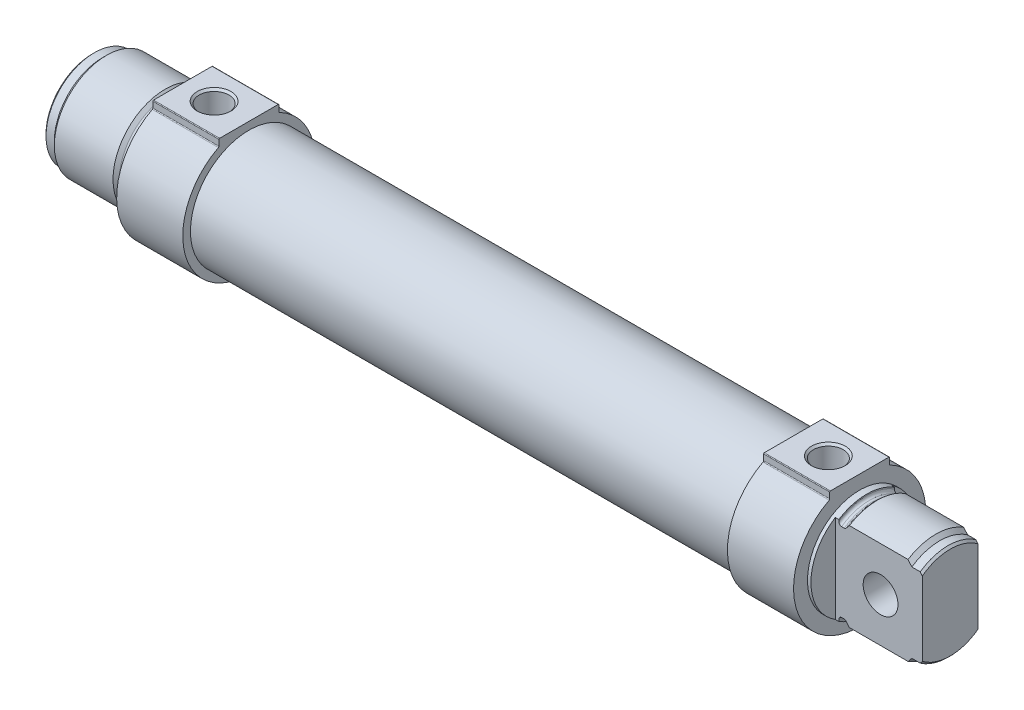
SolidWorks part; units mm, degrees
ref_plane "Ebene vorne" through (0, 0, 0) normal (0, 0, 1) x (1, 0, 0)
ref_plane "Ebene oben" through (0, 0, 0) normal (0, 1, 0) x (1, 0, 0)
ref_plane "Ebene rechts" through (0, 0, 0) normal (1, 0, 0) x (0, 0, -1)
sketch "Skizze1" plane through (0, 0, 0) normal (0, 0, 1) x (1, 0, 0)
  line L0 (0, 0) -> (0, 13.3)
  line L1 (0, 13.3) -> (0.6, 13.9)
  line L2 (0.6, 13.9) -> (3, 13.9)
  line L3 (3, 13.9) -> (4.1, 15)
  line L4 (4.1, 15) -> (20.95, 15)
  line L5 (20.95, 15) -> (21.8657, 14.0843)
  line L6 (22.4314, 13.85) -> (23.2, 13.85)
  line L7 (24, 14.65) -> (24, 15)
  line L8 (24, 15) -> (26, 15)
  line L9 (26, 15) -> (26, 0)
  line L10 (26, 0) -> (0, 0)
  line L11 (26, 0) -> (0, 0) construction
  arc A0 (21.8657, 14.0843) -> (22.4314, 13.85) centre (22.4314, 14.65) ccw
  arc A1 (23.2, 13.85) -> (24, 14.65) centre (23.2, 14.65) ccw
revolve "Rotation1" add sketch "Skizze1" angle 360 about L11 reverse direction yes
cosmetic thread "Gewindedarstellung1" parameters "D1"=17.77, "D2"=28.16
ref_plane "Ebene1" through (32, 0, 0) normal (1, 0, 0) x (0, 0, -1)
ref_plane "Ebene2" through (16, 0, 0) normal (1, 0, 0) x (0, 0, -1)
ref_plane "Ebene3" through (0, -20, 0) normal (0, 1, 0) x (1, 0, 0)
ref_plane "Ebene4" through (0, 15, 0) normal (0, 1, 0) x (1, 0, 0)
ref_plane "Ebene5" through (0, -9.5, 0) normal (0, 1, 0) x (1, 0, 0)
ref_plane "Ebene6" through (0, 9.5, 0) normal (0, 1, 0) x (1, 0, 0)
ref_plane "Ebene7" through (26, 0, 0) normal (1, 0, 0) x (0, 0, -1)
ref_plane "Ebene8" through (26, 0, 0) normal (1, 0, 0) x (0, 0, -1)
ref_plane "Ebene9" through (38.5, 0, 0) normal (1, 0, 0) x (0, 0, -1)
ref_plane "Ebene10" through (31, 0, 0) normal (1, 0, 0) x (0, 0, -1)
ref_plane "Ebene11" through (46, 0, 0) normal (1, 0, 0) x (0, 0, -1)
sketch "Skizze2" plane through (26, 0, 0) normal (1, 0, 0) x (0, 0, -1)
  line L0 (8.6, 17.1254) -> (8.6, 18.8)
  line L1 (8.4, 19) -> (-8.4, 19)
  line L2 (-8.6, 18.8) -> (-8.6, 17.1254)
  arc A0 (-8.7617, 16.8592) -> (8.7617, 16.8592) centre (0, 0) ccw
  arc A1 (8.7617, 16.8592) -> (8.6, 17.1254) centre (8.9, 17.1254) cw
  arc A2 (8.6, 18.8) -> (8.4, 19) centre (8.4, 18.8) ccw
  arc A3 (-8.4, 19) -> (-8.6, 18.8) centre (-8.4, 18.8) ccw
  arc A4 (-8.6, 17.1254) -> (-8.7617, 16.8592) centre (-8.9, 17.1254) cw
extrude "Aufsatz-Linear austragen1" add sketch "Skizze2" along normal blind 19
ref_plane "Ebene12" through (40.5, 0, 0) normal (1, 0, 0) x (0, 0, -1)
ref_plane "Ebene13" through (0, 0, 0) normal (0, 0, 1) x (1, 0, 0)
ref_plane "Ebene14" through (0, 0, -12.8) normal (0, 0, 1) x (1, 0, 0)
ref_plane "Ebene15" through (0, 0, 0) normal (0, 1, 0) x (1, 0, 0)
ref_plane "Ebene16" through (0, 9, 0) normal (0, 1, 0) x (1, 0, 0)
ref_plane "Ebene17" through (0, 0, -6.6) normal (0, 0, 1) x (1, 0, 0)
ref_plane "Ebene18" through (0, 0, 0) normal (0, 1, 0) x (1, 0, 0)
ref_plane "Ebene19" through (0, 9, 0) normal (0, 1, 0) x (1, 0, 0)
ref_plane "Ebene20" through (0, 9.8573, -1.7381) normal (0, 0.9848, -0.1736) x (1, 0, 0)
ref_plane "Ebene21" through (0, 8.3801, -1.4776) normal (0, 0.9848, -0.1736) x (1, 0, 0)
sketch "Skizze3" plane through (0, 0, 0) normal (0, 0, 1) x (1, 0, 0)
  line L0 (45, 0) -> (45, 16.8)
  line L1 (45, 16.8) -> (201.5, 16.8)
  line L2 (201.5, 16.8) -> (201.5, 0)
  line L3 (201.5, 0) -> (45, 0)
  line L4 (201.5, 0) -> (45, 0) construction
revolve "Rotation2" add sketch "Skizze3" angle 360 about L4 reverse direction yes
ref_plane "Ebene22" through (201.5, 0, 0) normal (1, 0, 0) x (0, 0, -1)
sketch "Skizze4" plane through (201.5, 0, 0) normal (1, 0, 0) x (0, 0, -1)
  line L0 (8.6, 17.1254) -> (8.6, 18.8)
  line L1 (8.4, 19) -> (-8.4, 19)
  line L2 (-8.6, 18.8) -> (-8.6, 17.1254)
  arc A0 (-8.7617, 16.8592) -> (8.7617, 16.8592) centre (0, 0) ccw
  arc A1 (8.7617, 16.8592) -> (8.6, 17.1254) centre (8.9, 17.1254) cw
  arc A2 (8.6, 18.8) -> (8.4, 19) centre (8.4, 18.8) ccw
  arc A3 (-8.4, 19) -> (-8.6, 18.8) centre (-8.4, 18.8) ccw
  arc A4 (-8.6, 17.1254) -> (-8.7617, 16.8592) centre (-8.9, 17.1254) cw
extrude "Aufsatz-Linear austragen2" add sketch "Skizze4" along normal blind 19
ref_plane "Ebene23" through (206, 0, 0) normal (1, 0, 0) x (0, 0, -1)
ref_plane "Ebene24" through (206, 0, 0) normal (1, 0, 0) x (0, 0, -1)
ref_plane "Ebene25" through (0, 0, 6.6) normal (0, 0, 1) x (1, 0, 0)
ref_plane "Ebene26" through (0, 0, 0) normal (0, 1, 0) x (1, 0, 0)
ref_plane "Ebene27" through (0, 9, 0) normal (0, 1, 0) x (1, 0, 0)
ref_plane "Ebene28" through (0, 9.8573, 1.7381) normal (0, 0.9848, 0.1736) x (1, 0, 0)
ref_plane "Ebene29" through (0, 8.3801, 1.4776) normal (0, 0.9848, 0.1736) x (1, 0, 0)
ref_plane "Ebene30" through (275.5, 0, 0) normal (1, 0, 0) x (0, 0, -1)
ref_plane "Ebene31" through (263, 0, 0) normal (1, 0, 0) x (0, 0, -1)
ref_plane "Ebene32" through (270.5, 0, 0) normal (1, 0, 0) x (0, 0, -1)
ref_plane "Ebene33" through (255.5, 0, 0) normal (1, 0, 0) x (0, 0, -1)
sketch "Skizze5" plane through (0, 0, 0) normal (0, 0, 1) x (1, 0, 0)
  line L0 (220.5, 0) -> (220.5, 15)
  line L1 (220.5, 15) -> (222.5, 15)
  line L2 (222.5, 15) -> (222.5, 14.65)
  line L3 (223.3, 13.85) -> (224.0686, 13.85)
  line L4 (224.6343, 14.0843) -> (225.55, 15)
  line L5 (225.55, 15) -> (242.4, 15)
  line L6 (242.4, 15) -> (243.5, 13.9)
  line L7 (243.5, 13.9) -> (245.9, 13.9)
  line L8 (245.9, 13.9) -> (246.5, 13.3)
  line L9 (246.5, 13.3) -> (246.5, 0)
  line L10 (246.5, 0) -> (220.5, 0)
  line L11 (246.5, 0) -> (220.5, 0) construction
  arc A0 (222.5, 14.65) -> (223.3, 13.85) centre (223.3, 14.65) ccw
  arc A1 (224.0686, 13.85) -> (224.6343, 14.0843) centre (224.0686, 14.65) ccw
revolve "Rotation3" add sketch "Skizze5" angle 360 about L11 reverse direction yes
cosmetic thread "Gewindedarstellung2" parameters "D1"=16.67, "D2"=28.16
sketch "Skizze6" plane through (0, 0, 0) normal (0, 1, 0) x (1, 0, 0)
  line L0 (221.5, 24) -> (221.5, 8)
  line L1 (221.5, 8) -> (246.5, 8)
  line L2 (246.5, 8) -> (246.5, -8)
  line L3 (246.5, -8) -> (221.5, -8)
  line L4 (221.5, -8) -> (221.5, -24)
  line L5 (221.5, -24) -> (262.5, -24)
  line L6 (262.5, -24) -> (262.5, 24)
  line L7 (262.5, 24) -> (221.5, 24)
extrude "Schnitt-Linear austragen1" cut sketch "Skizze6" along normal blind 19 and the other way blind 19
ref_plane "Ebene34" through (234.5, 0, 0) normal (1, 0, 0) x (0, 0, -1)
hole_wizard "Bohrung1" positions "Skizze8" profile "Skizze7" legacy
sketch "Skizze8" plane through (0, 0, -8) normal (0, 0, -1) x (-1, 0, 0)
  point P0 (-234.5, 0)
sketch "Skizze7" plane through (234.5, 0, -8) normal (1, 0, 0) x (0, 1, 0)
  line L0 (0, 0) -> (0, 16)
  line L1 (0, 16) -> (5, 16)
  line L2 (5, 16) -> (5, 0)
  line L3 (5, 0) -> (0, 0)
  line L4 (0, 110) -> (0, -10) construction
  dimension "Durchmesser" = 10
  dimension "Tiefe" = 16
hole_wizard "Bohrung2" positions "Skizze10" profile "Skizze9" legacy
sketch "Skizze10" plane through (0, 19, 0) normal (0, 1, 0) x (1, 0, 0)
  point P0 (35, 0)
sketch "Skizze9" plane through (35, 19, 0) normal (1, 0, 0) x (0, 0, 1)
  line L0 (0, 0) -> (0, 8.5)
  line L1 (0, 8.5) -> (4.283, 8.5)
  line L2 (4.283, 8.5) -> (4.283, 0.581)
  line L3 (4.283, 0.581) -> (4.864, 0)
  line L4 (4.864, 0) -> (0, 0)
  line L5 (0, -6.4453) -> (0, 115.525) construction
  line L6 (-4.283, 0.581) -> (-4.864, 0) construction
  dimension "Durchmesser" = 8.566
  dimension "Tiefe" = 8.5
  dimension "Senkwinkel1" = 90
  dimension "Senkdurchmesser3" = 9.728
cosmetic thread "Gewindedarstellung3" parameters "D1"=7, "D2"=9.728
hole_wizard "Bohrung3" positions "Skizze12" profile "Skizze11" legacy
sketch "Skizze12" plane through (0, 19, 0) normal (0, 1, 0) x (1, 0, 0)
  point P0 (211.5, 0)
sketch "Skizze11" plane through (211.5, 19, 0) normal (1, 0, 0) x (0, 0, 1)
  line L0 (0, 0) -> (0, 8.5)
  line L1 (0, 8.5) -> (4.283, 8.5)
  line L2 (4.283, 8.5) -> (4.283, 0.581)
  line L3 (4.283, 0.581) -> (4.864, 0)
  line L4 (4.864, 0) -> (0, 0)
  line L5 (0, -6.4453) -> (0, 115.525) construction
  line L6 (-4.283, 0.581) -> (-4.864, 0) construction
  dimension "Durchmesser" = 8.566
  dimension "Tiefe" = 8.5
  dimension "Senkwinkel1" = 90
  dimension "Senkdurchmesser3" = 9.728
cosmetic thread "Gewindedarstellung4" parameters "D1"=7, "D2"=9.728
sketch "Skizze13" plane through (0, 0, 0) normal (0, 0, 1) x (1, 0, 0)
  line L0 (-8, 0) -> (-8, 6)
  line L1 (-8, 6) -> (57, 6)
  line L2 (57, 6) -> (57, 16)
  line L3 (57, 16) -> (190, 16)
  line L4 (190, 16) -> (190, 0)
  line L5 (190, 0) -> (-8, 0)
  line L6 (190, 0) -> (-8, 0) construction
revolve "Schnitt-Rotation1" cut sketch "Skizze13" angle 360 about L6 reverse direction yes
ref_plane "Ebene35" through (-8, 0, 0) normal (1, 0, 0) x (0, 0, -1)
ref_plane "Ebene36" through (0, 19, 0) normal (0, 1, 0) x (1, 0, 0)
ref_plane "Ebene37" through (8.5, 0, 0) normal (1, 0, 0) x (0, 0, -1)
ref_plane "Ebene38" through (0, 0, 0) normal (1, 0, 0) x (0, 0, -1)
ref_plane "Ebene39" through (26, 0, 0) normal (1, 0, 0) x (0, 0, -1)
ref_plane "Ebene40" through (220.5, 0, 0) normal (1, 0, 0) x (0, 0, -1)
ref_plane "Ebene41" through (26, 0, 0) normal (1, 0, 0) x (0, 0, -1)
ref_plane "Ebene42" through (0, 19, 0) normal (0, 1, 0) x (1, 0, 0)
ref_plane "Ebene43" through (54.5, 0, 0) normal (1, 0, 0) x (0, 0, -1)
ref_plane "Ebene44" through (192, 0, 0) normal (1, 0, 0) x (0, 0, -1)
ref_plane "Ebene45" through (0, 0, 0) normal (0, 0, 1) x (1, 0, 0)
ref_plane "Ebene46" through (26, 0, 0) normal (1, 0, 0) x (0, 0, -1)
ref_plane "Ebene47" through (0, 19, 0) normal (0, 1, 0) x (1, 0, 0)
ref_plane "FDT_FRONT XY" through (26, 0, 0) normal (1, 0, 0) x (0, 0, -1)
ref_plane "FDT_FRONT XZ" through (0, 0, 0) normal (0, -1, 0) x (-1, 0, 0)
ref_plane "FDT_FRONT YZ" through (0, 0, 0) normal (0, 0, -1) x (-1, 0, 0)
ref_axis "FDT_FRONT X" through (26, 0, 80.9) along (0, 0, -1)
ref_axis "FDT_FRONT Y" through (26, -50, 0) along (0, 1, 0)
ref_axis "FDT_FRONT Z" through (80.9, 0, 0) along (-1, 0, 0)
sketch3d "FDT_FRONT"
  point P0 (26, 0, 0)
ref_plane "FDT_QSFRONT XY" through (0, 19, 0) normal (0, 1, 0) x (1, 0, 0)
ref_plane "FDT_QSFRONT XZ" through (35, 0, 0) normal (-1, 0, 0) x (0, 0, 1)
ref_plane "FDT_QSFRONT YZ" through (0, 0, 0) normal (0, 0, 1) x (1, 0, 0)
ref_axis "FDT_QSFRONT X" through (35, 19, -50) along (0, 0, 1)
ref_axis "FDT_QSFRONT Y" through (-80.9, 19, 0) along (1, 0, 0)
ref_axis "FDT_QSFRONT Z" through (35, 50, 0) along (0, -1, 0)
sketch3d "FDT_QSFRONT"
  point P0 (35, 19, 0)
ref_plane "FDT_QSREAR XY" through (0, 19, 0) normal (0, 1, 0) x (1, 0, 0)
ref_plane "FDT_QSREAR XZ" through (211.5, 0, 0) normal (-1, 0, 0) x (0, 0, 1)
ref_plane "FDT_QSREAR YZ" through (0, 0, 0) normal (0, 0, 1) x (1, 0, 0)
ref_axis "FDT_QSREAR X" through (211.5, 19, -50) along (0, 0, 1)
ref_axis "FDT_QSREAR Y" through (-80.9, 19, 0) along (1, 0, 0)
ref_axis "FDT_QSREAR Z" through (211.5, 50, 0) along (0, -1, 0)
sketch3d "FDT_QSREAR"
  point P0 (211.5, 19, 0)
ref_plane "FDT_REAR XY" through (220.5, 0, 0) normal (-1, 0, 0) x (0, 0, 1)
ref_plane "FDT_REAR XZ" through (0, 0, 0) normal (0, 1, 0) x (1, 0, 0)
ref_plane "FDT_REAR YZ" through (0, 0, 0) normal (0, 0, -1) x (-1, 0, 0)
ref_axis "FDT_REAR X" through (220.5, 0, 80.9) along (0, 0, -1)
ref_axis "FDT_REAR Y" through (220.5, 50, 0) along (0, -1, 0)
ref_axis "FDT_REAR Z" through (-80.9, 0, 0) along (1, 0, 0)
sketch3d "FDT_REAR"
  point P0 (220.5, 0, 0)
ref_plane "FDT_SMBR1 XY" through (54.5, 0, 0) normal (-1, 0, 0) x (0, 0, 1)
ref_plane "FDT_SMBR1 XZ" through (0, 0, 0) normal (0, -1, 0) x (-1, 0, 0)
ref_plane "FDT_SMBR1 YZ" through (0, 0, 0) normal (0, 0, 1) x (1, 0, 0)
ref_axis "FDT_SMBR1 X" through (54.5, 0, -80.9) along (0, 0, 1)
ref_axis "FDT_SMBR1 Y" through (54.5, -50, 0) along (0, 1, 0)
ref_axis "FDT_SMBR1 Z" through (-80.9, 0, 0) along (1, 0, 0)
sketch3d "FDT_SMBR1"
  point P0 (54.5, 0, 0)
ref_plane "FDT_SMBR2 XY" through (192, 0, 0) normal (-1, 0, 0) x (0, 0, 1)
ref_plane "FDT_SMBR2 XZ" through (0, 0, 0) normal (0, -1, 0) x (-1, 0, 0)
ref_plane "FDT_SMBR2 YZ" through (0, 0, 0) normal (0, 0, 1) x (1, 0, 0)
ref_axis "FDT_SMBR2 X" through (192, 0, -80.9) along (0, 0, 1)
ref_axis "FDT_SMBR2 Y" through (192, -50, 0) along (0, 1, 0)
ref_axis "FDT_SMBR2 Z" through (-80.9, 0, 0) along (1, 0, 0)
sketch3d "FDT_SMBR2"
  point P0 (192, 0, 0)
ref_plane "FDT_SWIVELAXIS XY" through (0, 0, 0) normal (0, 0, 1) x (1, 0, 0)
ref_plane "FDT_SWIVELAXIS XZ" through (0, 0, 0) normal (0, -1, 0) x (-1, 0, 0)
ref_plane "FDT_SWIVELAXIS YZ" through (234.5, 0, 0) normal (1, 0, 0) x (0, 0, -1)
ref_axis "FDT_SWIVELAXIS X" through (-80.9, 0, 0) along (1, 0, 0)
ref_axis "FDT_SWIVELAXIS Y" through (234.5, -50, 0) along (0, 1, 0)
ref_axis "FDT_SWIVELAXIS Z" through (234.5, 0, 80.9) along (0, 0, -1)
sketch3d "FDT_SWIVELAXIS"
  point P0 (234.5, 0, 0)
ref_plane "NUT XY" through (8.5, 0, 0) normal (1, 0, 0) x (0, 0, -1)
ref_plane "NUT XZ" through (0, 0, 0) normal (0, -1, 0) x (-1, 0, 0)
ref_plane "NUT YZ" through (0, 0, 0) normal (0, 0, -1) x (-1, 0, 0)
ref_axis "NUT X" through (8.5, 0, 80.9) along (0, 0, -1)
ref_axis "NUT Y" through (8.5, -50, 0) along (0, 1, 0)
ref_axis "NUT Z" through (80.9, 0, 0) along (-1, 0, 0)
sketch3d "NUT"
  point P0 (8.5, 0, 0)
ref_plane "ZR XY" through (0, 0, 0) normal (1, 0, 0) x (0, 0, -1)
ref_plane "ZR XZ" through (0, 0, 0) normal (0, -1, 0) x (-1, 0, 0)
ref_plane "ZR YZ" through (0, 0, 0) normal (0, 0, -1) x (-1, 0, 0)
ref_axis "ZR X" through (0, 0, 80.9) along (0, 0, -1)
ref_axis "ZR Y" through (0, -50, 0) along (0, 1, 0)
ref_axis "ZR Z" through (80.9, 0, 0) along (-1, 0, 0)
sketch3d "ZR"
  point P0 (0, 0, 0)
ref_plane "ZYL XY" through (26, 0, 0) normal (1, 0, 0) x (0, 0, -1)
ref_plane "ZYL XZ" through (0, 0, 0) normal (0, -1, 0) x (-1, 0, 0)
ref_plane "ZYL YZ" through (0, 0, 0) normal (0, 0, -1) x (-1, 0, 0)
ref_axis "ZYL X" through (26, 0, 80.9) along (0, 0, -1)
ref_axis "ZYL Y" through (26, -50, 0) along (0, 1, 0)
ref_axis "ZYL Z" through (80.9, 0, 0) along (-1, 0, 0)
sketch3d "ZYL"
  point P0 (26, 0, 0)
